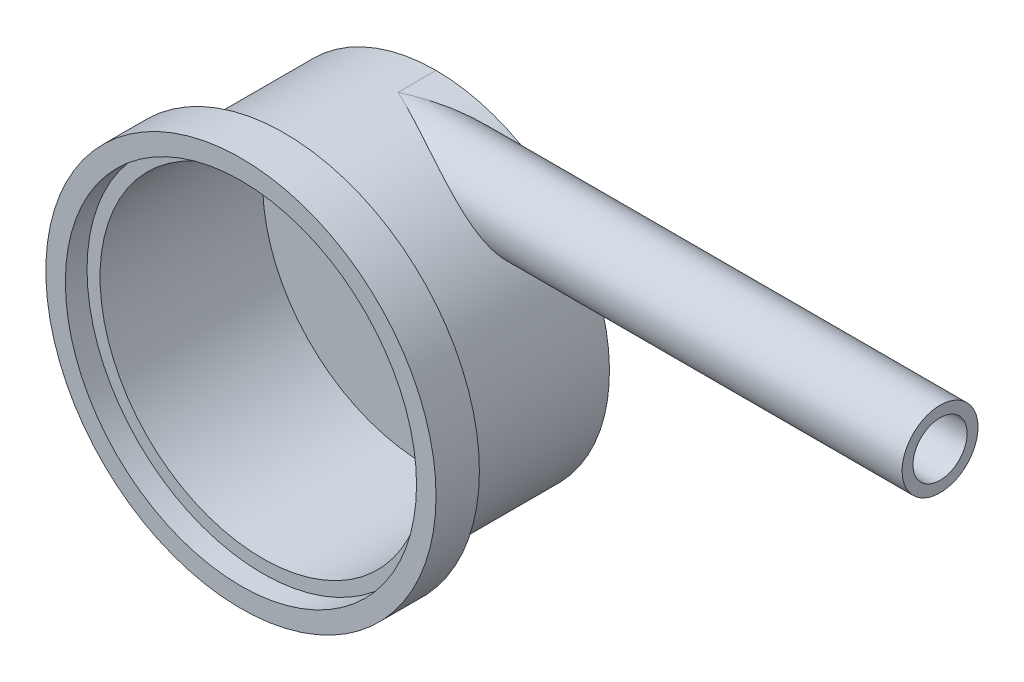
SolidWorks part; units mm, degrees
ref_plane "Front" through (0, 0, 0) normal (0, 0, 1) x (1, 0, 0)
ref_plane "Top" through (0, 0, 0) normal (0, 1, 0) x (1, 0, 0)
ref_plane "Right" through (0, 0, 0) normal (1, 0, 0) x (0, 0, -1)
sketch "Sketch1" plane through (0, 0, 0) normal (0, 0, 1) x (1, 0, 0)
  circle A0 centre (0, 0) radius 15 construction
  circle A1 centre (0, 0) radius 16
  dimension "Cavity_Diameter" = 30
  dimension "Wall_Thickness" = 1
extrude "Boss-Extrude Cavity" add sketch "Sketch1" along normal blind 15 contours A1
sketch "Sketch2" plane through (0, 0, 0) normal (1, 0, 0) x (0, 0, -1)
  line L0 (0, 16) -> (-15, 16) construction
  line L1 (0, -16) -> (0, 16) construction
  circle A0 centre (-2.5, 12.5) radius 3.5
  circle A1 centre (-2.5, 12.5) radius 2.5 construction
  dimension "D2" = 5
extrude "Boss-Extrude Inlet" add sketch "Sketch2" along normal blind 50
sketch "Sketch3" plane through (0, 0, 15) normal (0, 0, 1) x (1, 0, 0)
  circle A0 centre (0, 0) radius 15
  dimension "D1" = 30
extrude "Cut-Extrude1 Cavity" cut sketch "Sketch3" against normal through all both and the other way through all
sketch "Sketch4" plane through (50, 0, 0) normal (1, 0, 0) x (0, 0, -1)
  circle A0 centre (-2.5, 12.5) radius 2.5
  dimension "D1" = 5
extrude "Cut-Extrude2 Inlet" cut sketch "Sketch4" against normal up to next
sketch "Sketch5" plane through (0, 0, 0) normal (0, 0, -1) x (-1, 0, 0)
  circle A0 centre (0, 0) radius 16
  arc A1 (-12.4494, 10.0505) -> (-5.702, 14.9495) centre (0, 0) ccw construction
extrude "Boss-Extrude3 Cavity Wall" add sketch "Sketch5" along normal blind 1
sketch "Sketch6" plane through (0, 0, 15) normal (0, 0, 1) x (1, 0, 0)
  circle A0 centre (0, 0) radius 18
  circle A1 centre (0, 0) radius 16 construction
  circle A2 centre (0, 0) radius 16
  dimension "D1" = 2
extrude "Boss-Extrude4" add sketch "Sketch6" against normal blind 2
sketch "Sketch7" plane through (0, 0, 15) normal (0, 0, 1) x (1, 0, 0)
  circle A0 centre (0, 0) radius 18
  circle A1 centre (0, 0) radius 16.2
  circle A2 centre (0, 0) radius 18 construction
  circle A3 centre (0, 0) radius 15 construction
  dimension "D1" = 1.2
extrude "Boss-Extrude5" add sketch "Sketch7" along normal blind 2
equation "\"Wall_Thickness\"= 1"
equation "\"D1@Sketch2\"=\"Wall_Thickness\""
equation "\"Cavity_Diameter\"=30"
equation "\"Cavity_Diameter@Sketch1\"=\"Cavity_Diameter\""
equation "\"Wall_Thickness@Sketch1\"=\"Wall_Thickness\""
equation "\"Cavity_Length\"= 15"
equation "\"D1@Boss-Extrude Cavity\" = \"Cavity_Length\""
equation "\"Inlet_Diameter\" = 5"
equation "\"D2@Sketch2\"=\"Inlet_Diameter\""
equation "\"Inlet_Length\" = 50"
equation "\"D1@Boss-Extrude Inlet\" = \"Inlet_Length\""
equation "\"D1@Sketch3\"=\"Cavity_Diameter\""
equation "\"D1@Sketch4\"=\"Inlet_Diameter\""
equation "\"D1@Boss-Extrude3 Cavity Wall\" = \"Wall_Thickness\""
